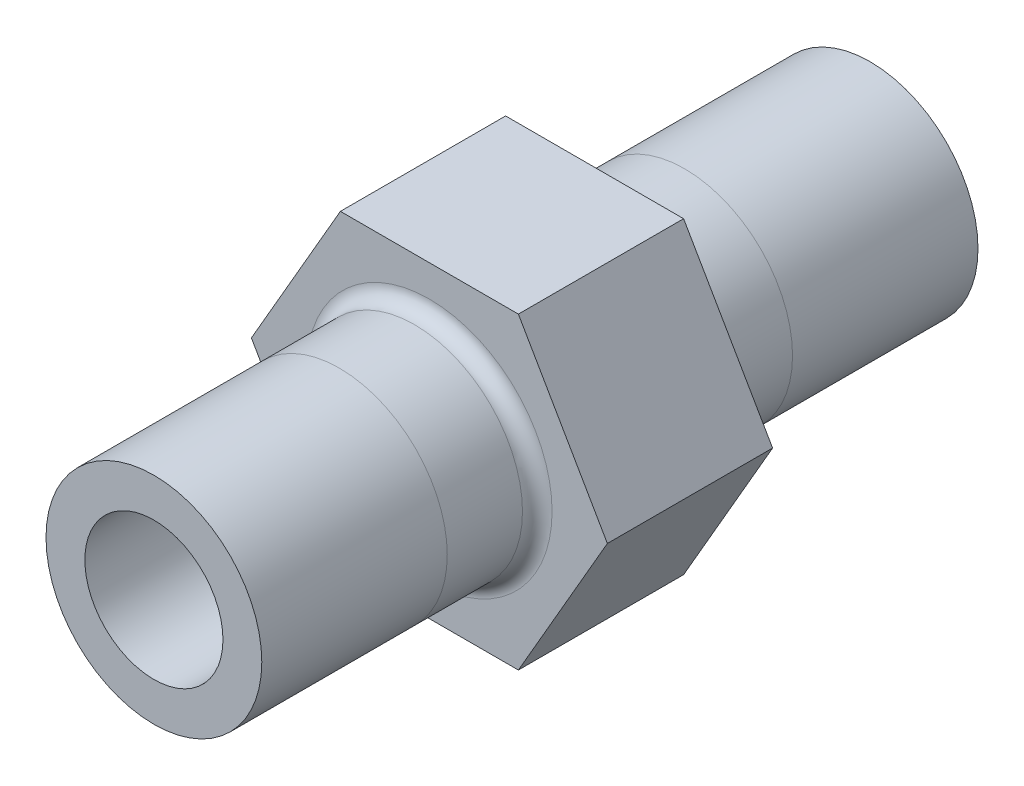
SolidWorks part; units mm, degrees
material "AISI 1020"
ref_plane "Front Plane" through (0, 0, 0) normal (0, 0, 1) x (1, 0, 0)
ref_plane "Top Plane" through (0, 0, 0) normal (0, 1, 0) x (1, 0, 0)
ref_plane "Right Plane" through (0, 0, 0) normal (1, 0, 0) x (0, 0, -1)
ref_axis "Axis1" through (0, 0, -88.99) along (0, 0, 1)
sketch "Sketch1" plane through (0, 0, 0) normal (0, 0, 1) x (1, 0, 0)
  circle A0 centre (0, 0) radius 5.5562
extrude "Boss-Extrude1" add sketch "Sketch1" along normal mid plane 36.8808 contours A0
sketch "Sketch3" plane through (0, 0, 0) normal (0, 0, 1) x (1, 0, 0)
  line L1 (9.1654, 0) -> (4.5827, 7.9375)
  line L2 (4.5827, 7.9375) -> (-4.5827, 7.9375)
  line L3 (-4.5827, 7.9375) -> (-9.1654, 0)
  line L4 (-9.1654, 0) -> (-4.5827, -7.9375)
  line L5 (-4.5827, -7.9375) -> (4.5827, -7.9375)
  line L6 (4.5827, -7.9375) -> (9.1654, 0)
  circle A0 centre (0, 0) radius 7.9375 construction
  dimension "D1" = 15.875
extrude "Boss-Extrude2" add sketch "Sketch3" along normal mid plane 8.509
sketch "Sketch2" plane through (0, 0, 18.4404) normal (0, 0, 1) x (1, 0, 0)
  circle A0 centre (0, 0) radius 3.556
extrude "Cut-Extrude1" cut sketch "Sketch2" against normal through all contours A0
fillet "Fillet1" radius 0.762 2 edges at (5.5562, 0, -4.2545) (5.5562, 0, 4.2545)
ref_plane "Plane1" through (0, 0, 8.89) normal (0, 0, 1) x (1, 0, 0)
split line "Split Line1"
ref_plane "Plane2" through (0, 0, -8.89) normal (0, 0, 1) x (1, 0, 0)
split line "Split Line2"
